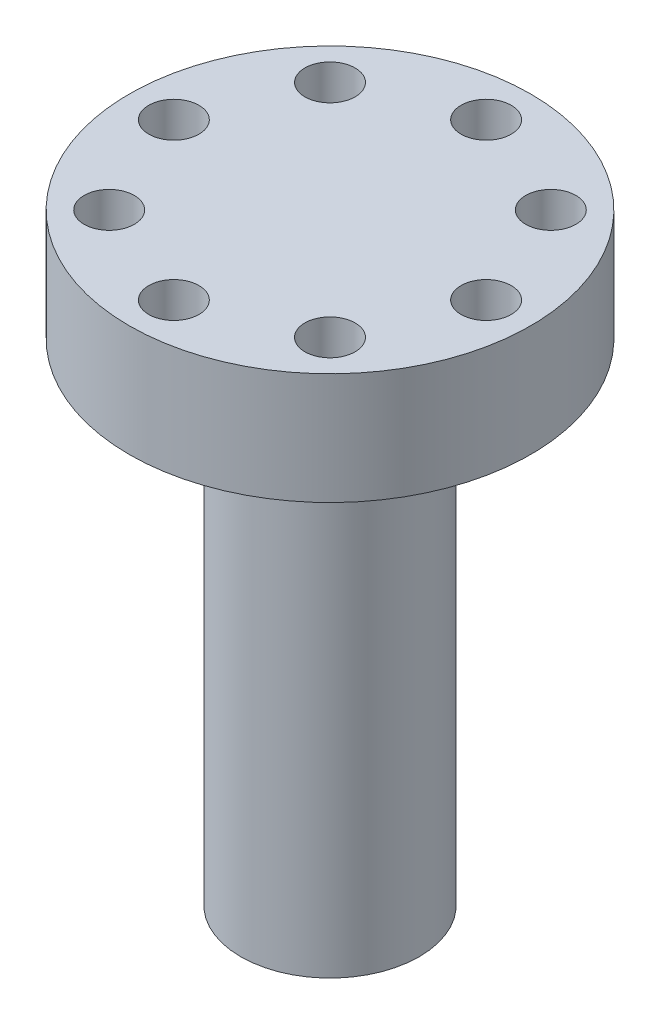
SolidWorks part; units mm, degrees
ref_plane "Front Plane" through (0, 0, 0) normal (0, 0, 1) x (1, 0, 0)
ref_plane "Top Plane" through (0, 0, 0) normal (0, 1, 0) x (1, 0, 0)
ref_plane "Right Plane" through (0, 0, 0) normal (1, 0, 0) x (0, 0, -1)
sketch "Sketch1" plane through (0, 0, 0) normal (0, 1, 0) x (1, 0, 0)
  circle A0 centre (0, 0) radius 9
  dimension "D1" = 18
extrude "BracketMount" add sketch "Sketch1" along normal blind 5
sketch "Sketch2" plane through (0, 5, 0) normal (0, 1, 0) x (1, 0, 0)
  circle A0 centre (0, 7) radius 1.125
  circle A7 centre (4.9497, 4.9497) radius 1.125
  circle A8 centre (7, 0) radius 1.125
  circle A9 centre (4.9497, -4.9497) radius 1.125
  circle A10 centre (0, -7) radius 1.125
  circle A11 centre (-4.9497, -4.9497) radius 1.125
  circle A12 centre (-7, 0) radius 1.125
  circle A13 centre (-4.9497, 4.9497) radius 1.125
  point P4 (0, 0)
  point P19 (0, 0)
  dimension "D1" = 2.25
  dimension "D3" = 7
extrude "Bracket-MountHoles" cut sketch "Sketch2" against normal up to surface (5 mm away) up to face at (0, 0, 9)
sketch "Sketch3" plane through (0, 0, 0) normal (0, -1, 0) x (1, 0, 0)
  circle A0 centre (0, 0) radius 4
  dimension "D1" = 8
extrude "StepperSleeve" add sketch "Sketch3" along normal blind 22
sketch "Sketch4" plane through (0, -22, 0) normal (0, -1, 0) x (1, 0, 0)
  circle A0 centre (0, 0) radius 2.51
  dimension "D1" = 5.02
extrude "InitialSeat" cut sketch "Sketch4" against normal blind 9
sketch "Sketch5" plane through (0, -13, 0) normal (0, -1, 0) x (1, 0, 0)
  line L3 (2.04, 1.4624) -> (2.04, -1.4624)
  arc A6 (2.04, 1.4624) -> (2.04, -1.4624) centre (0, 0) ccw
  point P1 (0, 0)
  point P2 (0, 0)
  point P4 (0, 0)
  point P7 (-2.51, 0)
  dimension "D1" = 4.55
extrude "OrientationNub" cut sketch "Sketch5" against normal up to surface (13 mm away) up to face at (0, 0, 4)
